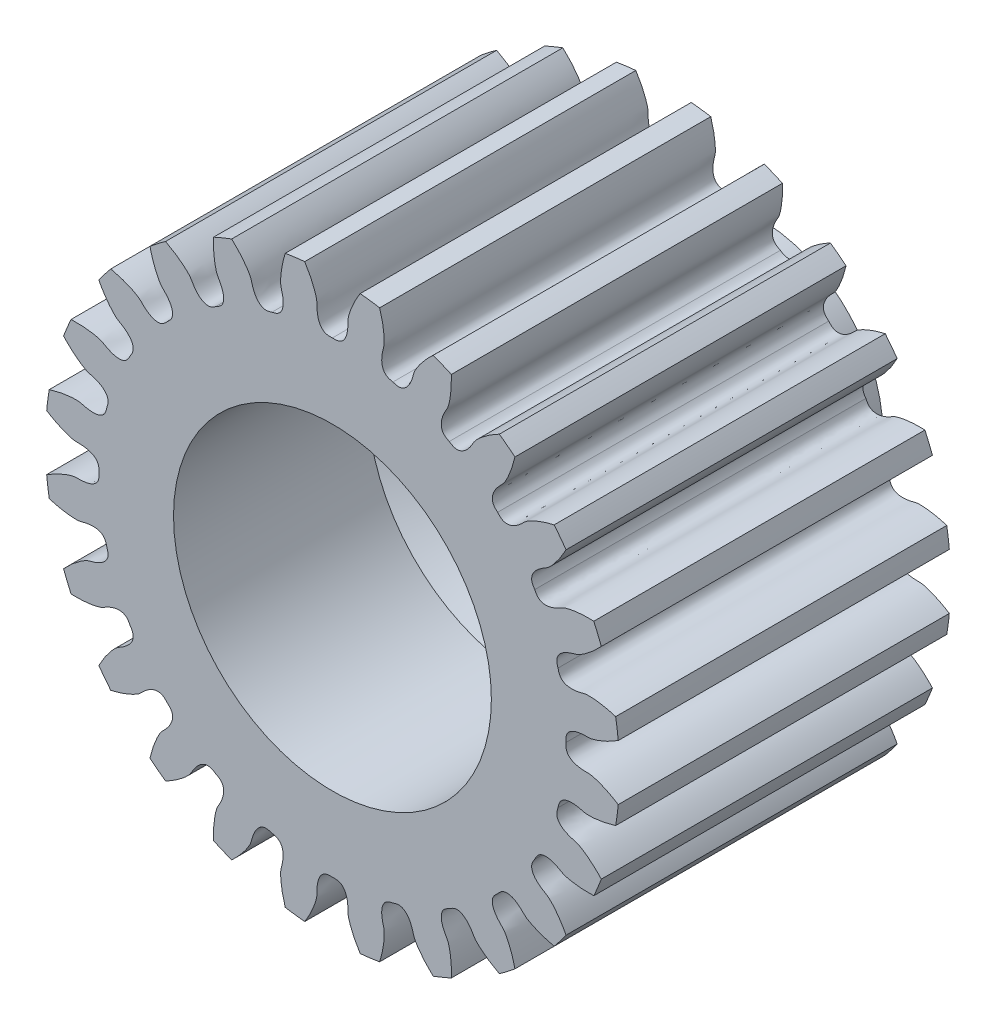
SolidWorks part; units mm, degrees
ref_plane "Alzado" through (0, 0, 0) normal (0, 0, 1) x (1, 0, 0)
ref_plane "Planta" through (0, 0, 0) normal (0, 1, 0) x (1, 0, 0)
ref_plane "Vista lateral" through (0, 0, 0) normal (1, 0, 0) x (0, 0, -1)
ref_axis "Eje1" through (0, 0, -88.99) along (0, 0, 1)
sketch "Gear-BaseSketch" plane through (0, 0, 0) normal (0, 0, 1) x (1, 0, 0)
  circle A0 centre (0, 0) radius 2.9482
  dimension "D1" = 5.8964
extrude "112.0 Diametral Pitch, 5,4429mm P.D." add sketch "Gear-BaseSketch" along normal mid plane 3.4
sketch "Tooth-Sketch; Backlash: 0,0000mm" plane through (0, 0, 0) normal (0, 0, 1) x (1, 0, 0)
  line L0 (0, 0) -> (0, 3.9521) construction
  arc A0 (-0.3448, 3.0224) -> (0.3448, 3.0224) centre (0, 0) cw
  spline S0 degree 3 poles (-0.3448, 3.0224) (-0.3231, 2.9931) (-0.2933, 2.9497) (-0.2585, 2.8917) (-0.2369, 2.8524) (-0.2185, 2.8158) (-0.2032, 2.7821) (-0.1906, 2.7514) (-0.1806, 2.7239) (-0.1728, 2.6998) (-0.1671, 2.6791) (-0.1569, 2.6392) (-0.1601, 2.6019) (-0.1579, 2.5685) (-0.157, 2.558) (-0.155, 2.5406) (-0.1509, 2.517) (-0.1437, 2.4905) (-0.1339, 2.466) (-0.1207, 2.4433) (-0.1025, 2.4223) (-0.0645, 2.3961) (-0.0251, 2.3967) (0, 2.3982) knots 0 0 0 0 0.142361 0.205915 0.264384 0.317769 0.36607 0.409287 0.447419 0.480467 0.508431 0.53131 0.641349 0.651929 0.662302 0.68244 0.720466 0.755956 0.789742 0.82316 0.858294 0.897791 1 1 1 1
  spline S1 degree 3 poles (0.3448, 3.0224) (0.3231, 2.9931) (0.2933, 2.9497) (0.2585, 2.8917) (0.2369, 2.8524) (0.2185, 2.8158) (0.2032, 2.7821) (0.1906, 2.7514) (0.1806, 2.7239) (0.1728, 2.6998) (0.1671, 2.6791) (0.1569, 2.6392) (0.1601, 2.6019) (0.1579, 2.5685) (0.157, 2.558) (0.155, 2.5406) (0.1509, 2.517) (0.1437, 2.4905) (0.1339, 2.466) (0.1207, 2.4433) (0.1025, 2.4223) (0.0645, 2.3961) (0.0251, 2.3967) (0, 2.3982) knots 0 0 0 0 0.142361 0.205915 0.264384 0.317769 0.36607 0.409287 0.447419 0.480467 0.508431 0.53131 0.641349 0.651929 0.662302 0.68244 0.720466 0.755956 0.789742 0.82316 0.858294 0.897791 1 1 1 1
extrude "Tooth-Cut, Fine Pitch Involute 14.5 deg" cut sketch "Tooth-Sketch; Backlash: 0,0000mm" against normal through all and the other way through all
pattern_circular "Tooth Pattern, 24 / 24" count 24 every 15 about axis through (0, 0, -88.99) along (0, 0, 1) of "Tooth-Cut, Fine Pitch Involute 14.5 deg"
hole_wizard "Taladro de margen para #42" positions "Croquis4" profile "Croquis5" hole size "#4" standard "Ansi Inch"
sketch "Croquis4" plane through (0, 0, 1.7) normal (0, 0, 1) x (1, 0, 0)
  point P0 (0, 0)
sketch "Croquis5" plane through (0, 0, 1.7) normal (1, 0, 0) x (0, -1, 0)
  line L0 (0, 0) -> (0, 2.9806)
  line L1 (0, 2.9806) -> (1.6319, 2)
  line L2 (1.6319, 2) -> (1.6319, 0)
  line L5 (1.6319, 0) -> (0, 0)
  line L10 (0, 2.9806) -> (-1.632, 2) construction
  line L11 (0, -6.35) -> (0, 107.95) construction
  dimension "Diámetro de taladro" = 3.2639
  dimension "Profundidad de taladro" = 2
  dimension "Ángulo de perforador" = 118
sketch "Croquis6" plane through (0, 0, -1.7) normal (0, 0, -1) x (-1, 0, 0)
  circle A0 centre (0, 0) radius 1.25
  dimension "D1" = 2.5
extrude "Saliente-Extruir2" add sketch "Croquis6" along normal blind 1
